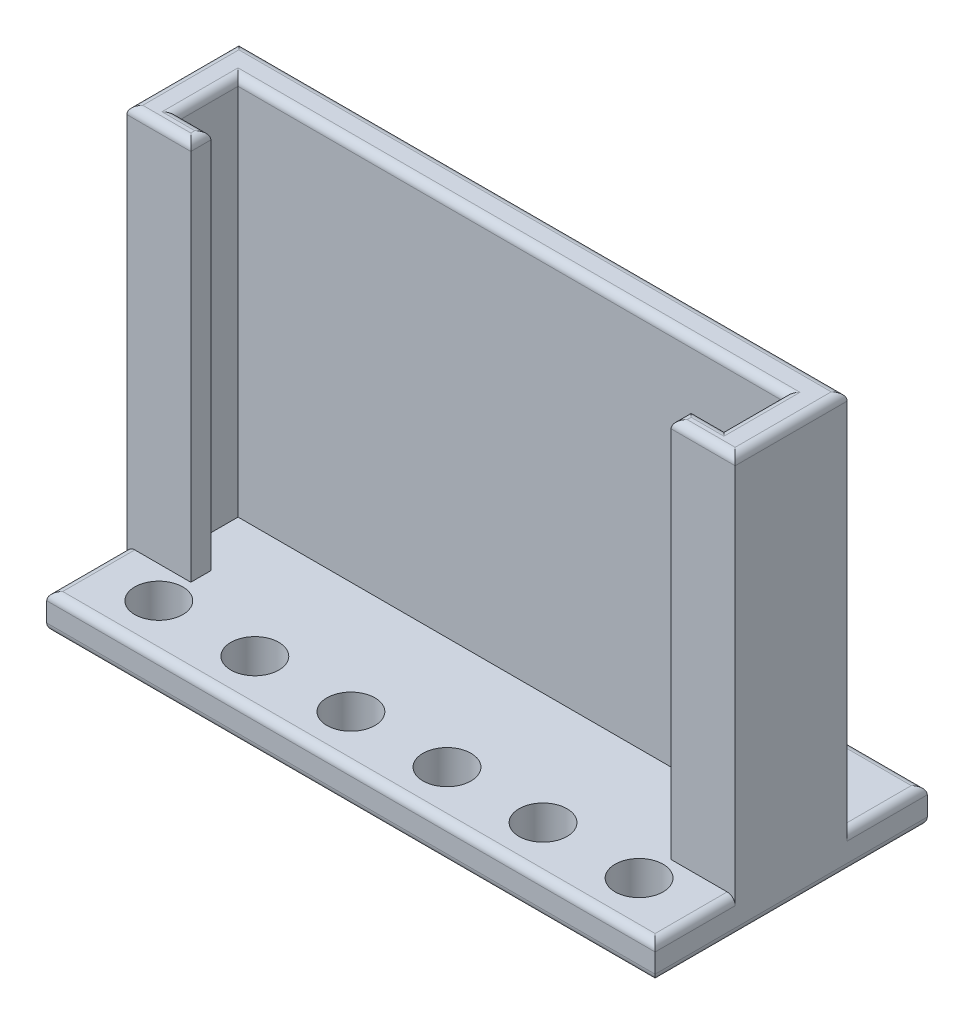
SolidWorks part; units mm, degrees
material "Copper"
ref_plane "Front Plane" through (0, 0, 0) normal (0, 0, 1) x (1, 0, 0)
ref_plane "Top Plane" through (0, 0, 0) normal (0, 1, 0) x (1, 0, 0)
ref_plane "Right Plane" through (0, 0, 0) normal (1, 0, 0) x (0, 0, -1)
sketch "Sketch2" plane through (0, 0, 0) normal (0, 0, 1) x (1, 0, 0)
  line L1 (0, 0) -> (96.52, 0)
  line L2 (0, 0) -> (0, 66.04)
  line L3 (0, 66.04) -> (96.52, 66.04)
  line L4 (96.52, 0) -> (96.52, 66.04)
  dimension "D1" = 96.52
  dimension "D2" = 66.04
extrude "Boss-Extrude1" add sketch "Sketch2" along normal blind 17.78
sketch "Sketch3" plane through (0, 0, 17.78) normal (0, 0, 1) x (1, 0, 0)
  line L0 (96.52, 0) -> (96.52, 66.04) construction
  line L1 (0, 0) -> (96.52, 0)
  line L2 (0, 0) -> (0, 5.588)
  line L3 (0, 5.588) -> (96.52, 5.588)
  line L4 (96.52, 0) -> (96.52, 5.588)
  dimension "D1" = 5.588
extrude "Boss-Extrude2" add sketch "Sketch3" along normal blind 12.7
sketch "Sketch4" plane through (0, 66.04, 0) normal (0, 1, 0) x (1, 0, 0)
  line L5 (0, -5.08) -> (4.953, -5.08) construction
  line L6 (0, -17.78) -> (0, 0) construction
  line L7 (96.52, -17.78) -> (96.52, 0) construction
  line L8 (0, -14.605) -> (4.953, -14.605) construction
  line L9 (4.953, -5.08) -> (91.567, -5.08)
  line L10 (4.953, -5.08) -> (4.953, -14.605)
  line L11 (4.953, -14.605) -> (91.567, -14.605)
  line L12 (91.567, -5.08) -> (91.567, -14.605)
  line L13 (91.567, -14.605) -> (96.52, -14.605) construction
  line L14 (91.567, -5.08) -> (96.52, -5.08) construction
  line L15 (96.52, -17.78) -> (0, -17.78) construction
  line L16 (10.16, -14.605) -> (86.36, -14.605)
  line L17 (10.16, -14.605) -> (10.16, -17.78)
  line L18 (10.16, -17.78) -> (86.36, -17.78)
  line L19 (86.36, -14.605) -> (86.36, -17.78)
  point P18 (48.26, -5.08)
  point P19 (48.26, -17.78)
  dimension "D1" = 86.614
  dimension "D2" = 9.525
  dimension "D3" = 3.175
  dimension "D4" = 76.2
extrude "Cut-Extrude1" cut sketch "Sketch4" against normal up to surface (60.452 mm away) contours L12 L9 L10 L11 | L18 L19 L16 L17 region at (48.26, 66.04, 9.8425) up to face at (48.26, 5.588, 24.13)
sketch "Sketch5" plane through (0, 0, 0) normal (0, 0, -1) x (-1, 0, 0)
  line L0 (0, 66.04) -> (0, 0) construction
  line L1 (-96.52, 0) -> (0, 0)
  line L2 (-96.52, 0) -> (-96.52, 5.588)
  line L3 (-96.52, 5.588) -> (0, 5.588)
  line L4 (0, 0) -> (0, 5.588)
  dimension "D1" = 5.588
extrude "Boss-Extrude3" add sketch "Sketch5" along normal blind 12.7
sketch "Sketch6" plane through (0, 5.588, 0) normal (0, 1, 0) x (1, 0, 0)
  line L0 (96.52, -22.86) -> (86.36, -22.86) construction
  line L3 (96.52, 6.35) -> (86.36, 6.35) construction
  line L4 (96.52, 12.7) -> (96.52, 0) construction
  line L5 (0, 12.7) -> (0, 0) construction
  line L6 (86.36, 6.35) -> (10.16, 6.35) construction
  line L7 (10.16, 6.35) -> (0, 6.35) construction
  line L8 (10.16, -22.86) -> (0, -22.86) construction
  line L9 (96.52, -30.48) -> (96.52, -17.78) construction
  line L10 (0, -30.48) -> (0, -17.78) construction
  circle A0 centre (10.16, 6.35) radius 2.413
  circle A1 centre (22.86, 6.35) radius 2.413
  circle A2 centre (35.56, 6.35) radius 2.413
  circle A3 centre (48.26, 6.35) radius 2.413
  circle A4 centre (60.96, 6.35) radius 2.413
  circle A5 centre (73.66, 6.35) radius 2.413
  circle A6 centre (86.36, 6.35) radius 2.413
  circle A7 centre (10.16, -22.86) radius 3.81
  circle A8 centre (25.4, -22.86) radius 3.81
  circle A9 centre (40.64, -22.86) radius 3.81
  circle A10 centre (55.88, -22.86) radius 3.81
  circle A11 centre (71.12, -22.86) radius 3.81
  circle A12 centre (86.36, -22.86) radius 3.81
  dimension "D1" = 4.826
  dimension "D4" = 7.62
  dimension "D3" = 12.7
  dimension "D6" = 15.24
  dimension "D7" = 5.08
  dimension "D2" = 7
  dimension "D5" = 6
extrude "Cut-Extrude2" cut sketch "Sketch6" against normal through all
fillet "Fillet1" radius 1.27 12 edges at (88.9635, 66.04, 14.605) (91.567, 66.04, 9.8425) (48.26, 66.04, 5.08) (4.953, 66.04, 9.8425) (7.5565, 66.04, 14.605) (10.16, 66.04, 16.1925) (5.08, 66.04, 17.78) (0, 66.04, 8.89) (48.26, 66.04, 0) (96.52, 66.04, 8.89) (91.44, 66.04, 17.78) (86.36, 66.04, 16.1925)
fillet "Fillet2" radius 1.27 6 edges at (96.52, 5.588, -6.35) (48.26, 5.588, -12.7) (0, 5.588, -6.35) (96.52, 5.588, 24.13) (48.26, 5.588, 30.48) (0, 5.588, 24.13)
fillet "Fillet3" radius 1.27 4 edges at (48.26, 0, -12.7) (96.52, 0, 8.89) (48.26, 0, 30.48) (0, 0, 8.89)
